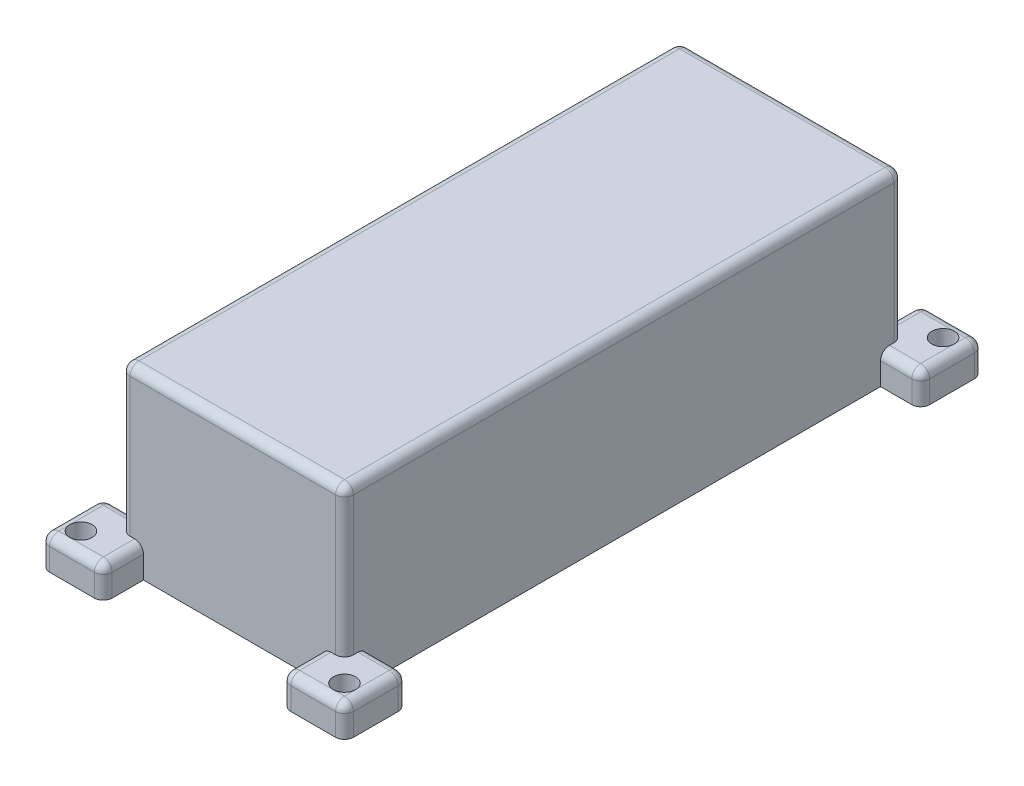
SolidWorks part; units mm, degrees
material "ABS"
ref_plane "Front Plane" through (0, 0, 0) normal (0, 0, 1) x (1, 0, 0)
ref_plane "Top Plane" through (0, 0, 0) normal (0, 1, 0) x (1, 0, 0)
ref_plane "Right Plane" through (0, 0, 0) normal (1, 0, 0) x (0, 0, -1)
sketch "Sketch1" plane through (0, 0, 0) normal (0, 1, 0) x (1, 0, 0)
  line L1 (-25, -62.5) -> (25, -62.5)
  line L2 (-25, -62.5) -> (-25, 62.5)
  line L3 (-25, 62.5) -> (25, 62.5)
  line L4 (25, -62.5) -> (25, 62.5)
  line L5 (-25, -62.5) -> (25, 62.5) construction
  line L6 (-25, 62.5) -> (25, -62.5) construction
  point P0 (0, 0)
  dimension "D1" = 125
  dimension "D2" = 50
extrude "Boss-Extrude1" add sketch "Sketch1" along normal blind 40
shell "Shell2" thickness 2
sketch "Sketch3" plane through (0, 0, 0) normal (0, 1, 0) x (1, 0, 0)
  line L0 (25, -62.5) -> (20, -62.5)
  line L1 (-25, -62.5) -> (25, -62.5) construction
  line L2 (20, -62.5) -> (20, -71.5)
  line L3 (20, -71.5) -> (34, -71.5)
  line L4 (34, -71.5) -> (34, -57.5)
  line L5 (34, -57.5) -> (25, -57.5)
  line L6 (25, -62.5) -> (25, 62.5) construction
  line L7 (25, -57.5) -> (25, -62.5)
  circle A1 centre (29.5, -67) radius 2.5
  point P13 (29.5, -57.5)
  point P14 (20, -67)
  dimension "D1" = 5
  dimension "D2" = 9
  dimension "D3" = 5
extrude "Boss-Extrude2" add sketch "Sketch3" along normal blind 7
mirror "Mirror2" about plane through (0, 0, 0) normal (0, 0, 1) of "Boss-Extrude2" second plane through (0, 0, 0) second plane normal (1, 0, 0)
sketch "Sketch4" plane through (0, 0, -62.5) normal (0, 0, -1) x (-1, 0, 0)
  line L0 (-20, 0) -> (20, 0) construction
  line L1 (-5, 0) -> (5, 0)
  line L2 (-5, 0) -> (-5, 25)
  line L3 (-5, 25) -> (5, 25)
  line L4 (5, 0) -> (5, 25)
  line L5 (-25, 40) -> (25, 40) construction
  point P6 (0, 0)
  point P7 (0, 0)
  dimension "D1" = 10
  dimension "D2" = 15
extrude "Cut-Extrude1" cut sketch "Sketch4" against normal up to next
fillet "Fillet2" radius 2 36 edges at (-25, 40, 0) (0, 40, 62.5) (20, 7, 67) (27, 7, 71.5) (34, 7, 64.5) (29.5, 7, 57.5) (20, 3.5, 71.5) (34, 3.5, 71.5) (34, 3.5, 57.5) (-29.5, 7, 57.5) (-34, 7, 64.5) (-34, 3.5, 57.5) (25, 40, 0) (-27, 7, 71.5) (-34, 3.5, 71.5) (-20, 7, 67) (-20, 3.5, 71.5) (29.5, 7, -57.5) (34, 7, -64.5) (34, 3.5, -57.5) (27, 7, -71.5) (34, 3.5, -71.5) (20, 7, -67) (20, 3.5, -71.5) (25, 23.5, 62.5) (-25, 23.5, 62.5) (-25, 23.5, -62.5) (25, 23.5, -62.5) (-20, 7, -67) (-27, 7, -71.5) (-34, 7, -64.5) (-29.5, 7, -57.5) (-20, 3.5, -71.5) (-34, 3.5, -71.5) (-34, 3.5, -57.5) (0, 40, -62.5)
fillet "Fillet3" radius 2 2 edges at (5, 25, -61.5) (-5, 25, -61.5)
